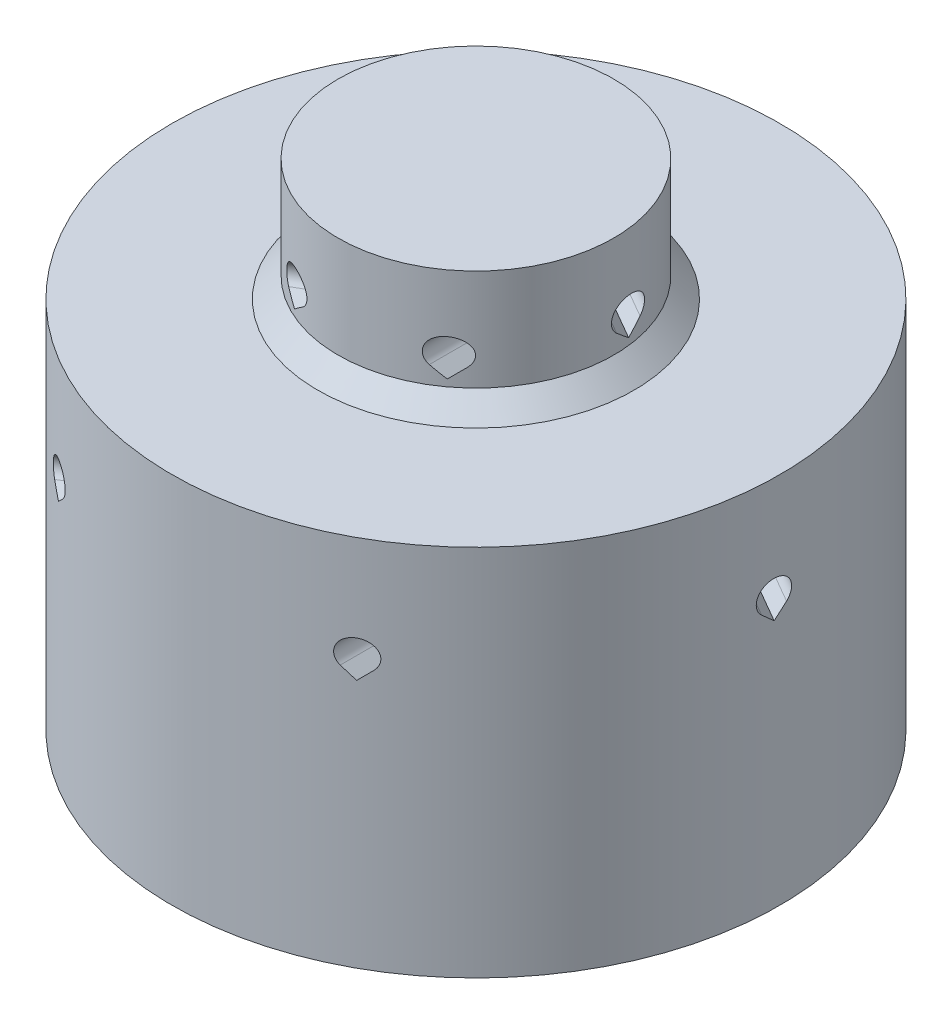
SolidWorks part; units mm, degrees
material "ASTM A36 Steel"
ref_plane "Front Plane" through (0, 0, 0) normal (0, 0, 1) x (1, 0, 0)
ref_plane "Top Plane" through (0, 0, 0) normal (0, 1, 0) x (1, 0, 0)
ref_plane "Right Plane" through (0, 0, 0) normal (1, 0, 0) x (0, 0, -1)
ref_axis "Axis1" through (0, 42.935, 0) along (0, -1, 0)
sketch "Sketch1" plane through (0, 0, 0) normal (0, 0, 1) x (1, 0, 0)
  line L1 (-5.3975, 0) -> (-5.3975, -3.9688)
  line L2 (-6.1912, -4.7625) -> (-11.9062, -4.7625)
  line L3 (-11.9062, -4.7625) -> (-11.9062, -7.1755)
  line L7 (-3.81, -1.5875) -> (-3.81, -13.0175)
  line L8 (-3.81, -13.0175) -> (-2.54, -14.2875)
  line L9 (-2.54, -14.2875) -> (-2.54, -16.8275)
  line L10 (-2.54, -16.8275) -> (-3.3337, -16.8275)
  line L11 (-3.3337, -16.8275) -> (-3.3337, -14.6163)
  line L12 (-3.3337, -14.6163) -> (-4.6037, -13.3463)
  line L13 (-4.6037, -13.3463) -> (-4.6037, -7.9375)
  line L14 (0, -1.5875) -> (0, -17.8202) construction
  line L15 (-4.6037, -7.9375) -> (-6.35, -7.9375)
  line L16 (-6.35, -7.9375) -> (-6.35, -7.1755)
  line L17 (-6.35, -7.1755) -> (-11.9062, -7.1755)
  line L19 (-5.3975, 0) -> (-4.445, 0)
  line L20 (-4.445, 0) -> (-4.445, -1.5875)
  line L21 (-4.445, -1.5875) -> (-3.81, -1.5875)
  line L22 (-6.1912, -4.7625) -> (-5.3975, -3.9688)
  point P10 (-6.35, -7.5565)
  dimension "D1" = 3.81
  dimension "D2" = 2.54
  dimension "D3" = 135
  dimension "D4" = 11.43
  dimension "D5" = 2.54
  dimension "D6" = 1.5875
  dimension "D7" = 3.175
  dimension "D8" = 0.7937
  dimension "D9" = 0.7937
  dimension "D10" = 0.762
  dimension "D11" = 1.5875
  dimension "D12" = 11.9062
  dimension "D13" = 3.175
  dimension "D14" = 135
  dimension "D15" = 6.35
  dimension "D16" = 4.445
  dimension "D17" = 0.7937
  dimension "D18" = 0.7937
revolve "Revolve1" add sketch "Sketch1" angle 360 about L14
sketch "Sketch2" plane through (0, 0, 0) normal (0, 0, 1) x (1, 0, 0)
  line L0 (-6.35, -7.9375) -> (-6.35, -14.2875)
  line L1 (-6.35, -7.1755) -> (-11.9062, -7.1755) construction
  line L2 (-6.35, -14.2875) -> (-4.445, -16.1925)
  line L3 (-4.445, -16.1925) -> (-4.445, -22.5425)
  line L4 (-4.445, -22.5425) -> (-6.35, -22.5425)
  line L5 (-6.35, -22.5425) -> (-6.35, -19.3675)
  line L7 (-11.9062, -7.1755) -> (-11.9062, -19.3675)
  line L8 (-10.3886, -19.3675) -> (-11.9062, -19.3675)
  line L9 (0, 42.935) -> (0, -67.065) construction
  line L10 (-6.35, -7.9375) -> (-6.35, -7.1755)
  line L11 (-6.35, -7.1755) -> (-11.9062, -7.1755)
  line L13 (0, -1.5875) -> (0, -17.8202) construction
  line L14 (-6.35, -19.3675) -> (-7.3152, -19.3675)
  line L15 (-7.3152, -19.3675) -> (-7.3152, -17.3863)
  line L16 (-7.3152, -17.3863) -> (-10.3886, -17.3863)
  line L17 (-10.3886, -17.3863) -> (-10.3886, -19.3675)
  point P2 (-11.8448, -7.1755)
  point P18 (-11.9062, -7.1755)
  dimension "D1" = 4.445
  dimension "D2" = 3.175
  dimension "D3" = 135
  dimension "D4" = 6.35
  dimension "D5" = 6.35
  dimension "D6" = 6.35
  dimension "D7" = 3.0734
  dimension "D8" = 1.9812
  dimension "D9" = 10.3886
revolve "Revolve2" add sketch "Sketch2" angle 360 about L14
sketch "Sketch3" plane through (0, 0, 0) normal (0, 0, 1) x (1, 0, 0)
  line L0 (-4.445, -1.5875) -> (0, -1.5875)
  line L1 (4.445, -1.5875) -> (-4.445, -1.5875) construction
  line L2 (0, -1.5875) -> (0, 0)
  line L3 (0, 0) -> (-4.445, 0)
  line L4 (-4.445, 0) -> (-4.445, -1.5875)
revolve "Revolve3" add sketch "Sketch3" angle 360 about L2
sketch "Sketch8" plane through (0, 0, 0) normal (0, 0, 1) x (1, 0, 0)
  line L0 (-3.2147, -3.6994) -> (-3.6356, -3.2784)
  line L1 (-2.7937, -3.2784) -> (-3.2147, -3.6994)
  line L2 (-3.2147, -2.8575) -> (-3.2147, -3.6994) construction
  line L3 (-3.81, -1.5875) -> (-3.81, -13.0175) construction
  line L4 (5.3975, 0) -> (-5.3975, 0) construction
  arc A0 (-3.6356, -3.2784) -> (-2.7937, -3.2784) centre (-3.2147, -2.8575) cw
  point P4 (-3.5416, -4.5666)
  point P5 (-3.81, -2.8575)
  point P6 (0, 0)
  point P7 (0, 0)
  dimension "D2" = 0.5953
  dimension "D1" = 90
  dimension "D3" = 2.8575
extrude "Cut-Extrude1" cut sketch "Sketch8" against normal through all
pattern_circular "CirPattern1" count 6 over 360 about axis through (0, 42.935, 0) along (0, -1, 0) of "Cut-Extrude1"
sketch "Sketch9" plane through (0, 0, 0) normal (0, 0, 1) x (1, 0, 0)
  line L0 (-5.7547, -9.6049) -> (-6.1756, -9.1839)
  line L1 (-5.3337, -9.1839) -> (-5.7547, -9.6049)
  line L2 (-5.7547, -9.6049) -> (-5.7547, -8.763) construction
  line L3 (-6.35, -7.9375) -> (-6.35, -14.2875) construction
  line L5 (-6.35, -7.1755) -> (-11.9062, -7.1755) construction
  arc A0 (-6.1756, -9.1839) -> (-5.3337, -9.1839) centre (-5.7547, -8.763) cw
  point P4 (-6.35, -8.763)
  point P5 (0, 0)
  dimension "D2" = 0.5953
  dimension "D1" = 90
  dimension "D3" = 1.5875
extrude "Cut-Extrude2" cut sketch "Sketch9" against normal through all
pattern_circular "CirPattern2" count 6 over 360 about axis through (0, 42.935, 0) along (0, -1, 0) of "Cut-Extrude2"
ref_axis "Axis2" through (13.97, 0, 0) along (-1, 0, 0)
ref_axis "Axis3" through (0, 0, -13.97) along (0, 0, 1)
equation "\"D2@Sketch9\"=3/128"
equation "\".o625\"=0.0585896"
